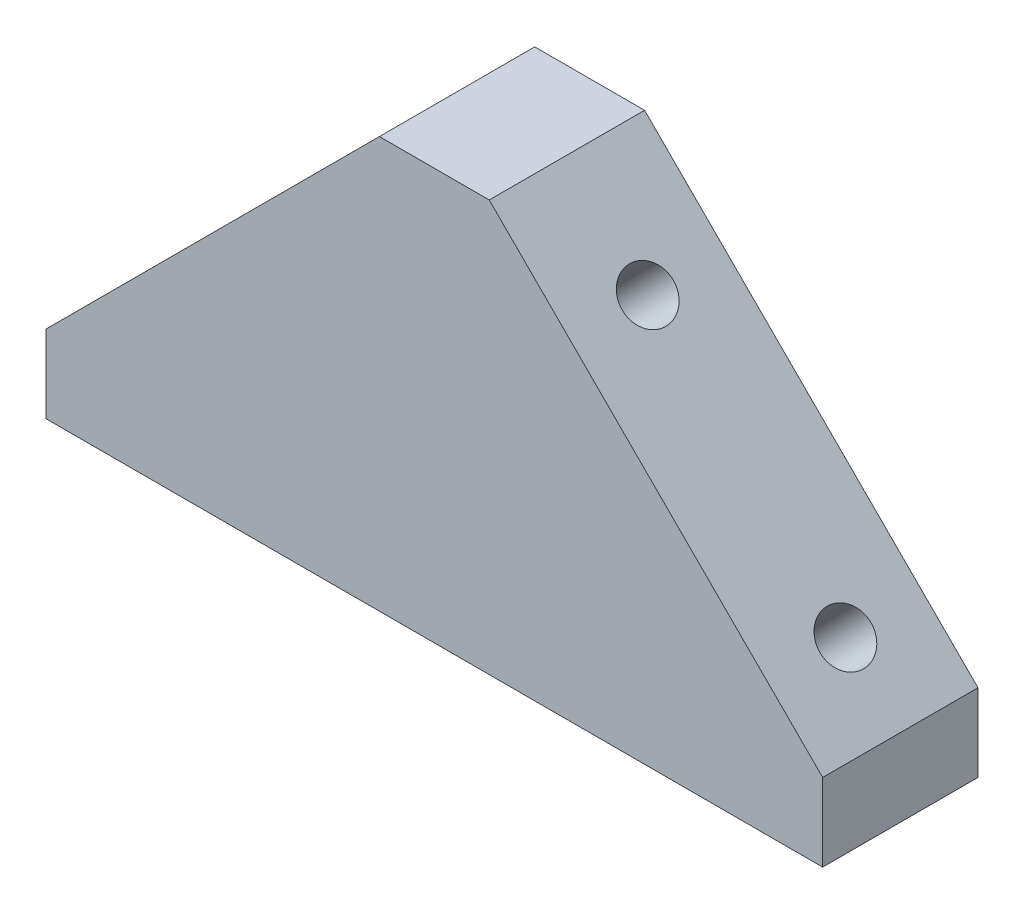
SolidWorks part; units mm, degrees
ref_plane "Front" through (0, 0, 0) normal (0, 0, 1) x (1, 0, 0)
ref_plane "Top" through (0, 0, 0) normal (0, 1, 0) x (1, 0, 0)
ref_plane "Right" through (0, 0, 0) normal (1, 0, 0) x (0, 0, -1)
sketch "Esquisse1" plane through (0, 0, 0) normal (0, 0, 1) x (1, 0, 0)
  line L0 (-25, 0) -> (25, 0)
  line L1 (25, 0) -> (25, 5)
  line L2 (25, 5) -> (0, 30)
  line L3 (0, 30) -> (0, 0) construction
  line L4 (-25, 5) -> (0, 30)
  line L5 (-25, 0) -> (-25, 5)
  point P5 (25, 2.5)
  dimension "D1" = 50
  dimension "D2" = 45
  dimension "D3" = 5
extrude "Boss.-Extru.1" add sketch "Esquisse1" along normal blind 10
sketch "Esquisse2" plane through (15, 15, 0) normal (0.7071, 0.7071, 0) x (0, 0, -1)
  line L0 (-5, -14.1421) -> (-5, 21.2132) construction
  line L1 (-10, -14.1421) -> (0, -14.1421) construction
  line L2 (-10, 21.2132) -> (0, 21.2132) construction
  circle A0 centre (-5, 8.8579) radius 1.65
  circle A1 centre (-5, -9.1421) radius 1.65
  dimension "D1" = 18
  dimension "D2" = 3.3
  dimension "D3" = 5
extrude "Enlèv. mat.-Extru.1" cut sketch "Esquisse2" against normal blind 8
sketch "Esquisse3" plane through (-15, 15, 0) normal (-0.7071, 0.7071, 0) x (0, 0, 1)
  line L0 (5, -14.1421) -> (5, 21.2132) construction
  line L1 (10, -14.1421) -> (0, -14.1421) construction
  line L2 (10, 21.2132) -> (0, 21.2132) construction
  circle A0 centre (5, 9.8579) radius 1.65
  circle A1 centre (5, -8.1421) radius 1.65
  dimension "D1" = 18
  dimension "D2" = 3.3
  dimension "D3" = 6
extrude "Enlèv. mat.-Extru.2" cut sketch "Esquisse3" against normal blind 8
chamfer "Chanfrein1" distance 5 angle 45 1 edges at (0, 30, 5)
